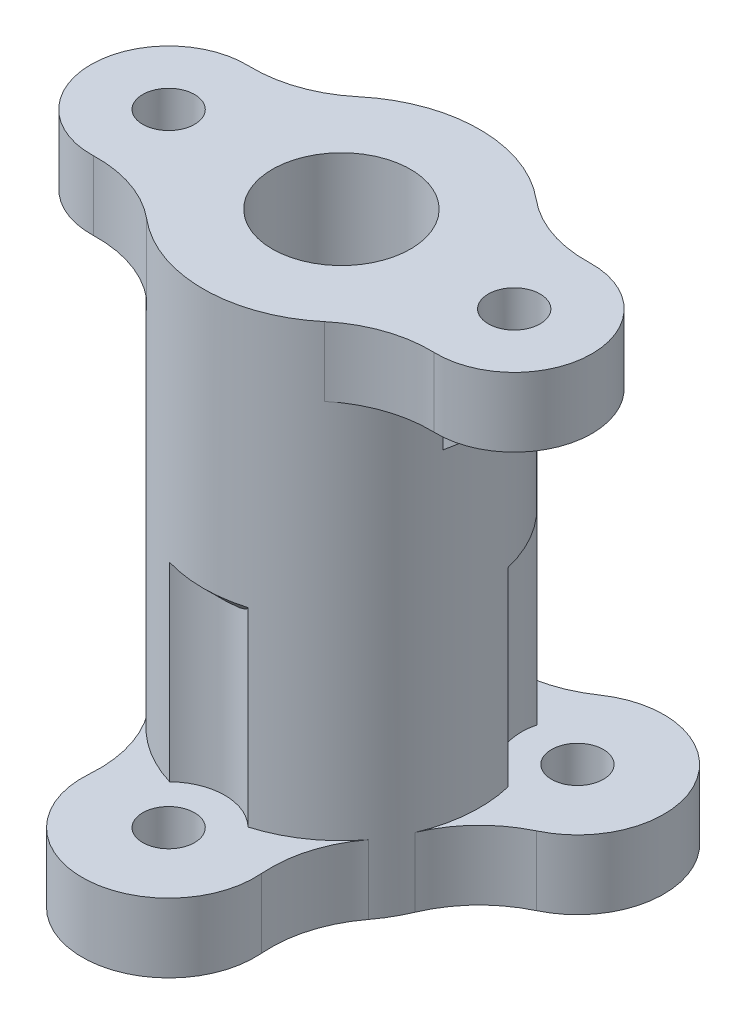
SolidWorks part; units mm, degrees
ref_plane "Спереди" through (0, 0, 0) normal (0, 0, 1) x (1, 0, 0)
ref_plane "Сверху" through (0, 0, 0) normal (0, 1, 0) x (1, 0, 0)
ref_plane "Справа" through (0, 0, 0) normal (1, 0, 0) x (0, 0, -1)
sketch "Sketch1" plane through (0, 0, 0) normal (0, 1, 0) x (1, 0, 0)
  circle A0 centre (0, 0) radius 4
  circle A1 centre (0, 0) radius 8
  dimension "D1" = 8
  dimension "D2" = 4
extrude "Boss-Extrude1" add sketch "Sketch1" along normal blind 30
sketch "Sketch2" plane through (0, 30, 0) normal (0, 1, 0) x (1, 0, 0)
  line L0 (0, 5.7735) -> (0, 0) construction
  circle A0 centre (-10, 0) radius 1.5
  circle A2 centre (-10, 0) radius 4.5
  circle A3 centre (10, 0) radius 4.5
  circle A4 centre (10, 0) radius 1.5
  dimension "D1" = 3
  dimension "D2" = 9
  dimension "D3" = 20
extrude "Boss-Extrude2" add sketch "Sketch2" against normal blind 4
fillet "Fillet1" radius 7 4 edges at (7.1875, 28, 3.5128) (7.1875, 28, -3.5128) (-7.1875, 28, -3.5128) (-7.1875, 28, 3.5128)
sketch "Sketch3" plane through (0, 0, 0) normal (0, -1, 0) x (1, 0, 0)
  circle A0 centre (0, 10) radius 1.5
  circle A1 centre (0, 10) radius 5
  circle A2 centre (8.6603, -5) radius 1.5
  circle A3 centre (8.6603, -5) radius 5
  circle A4 centre (-8.6603, -5) radius 1.5
  circle A5 centre (-8.6603, -5) radius 5
  point P13 (0, 0)
  dimension "D1" = 3
  dimension "D3" = 10
  dimension "D2" = 10
extrude "Boss-Extrude3" add sketch "Sketch3" against normal blind 4
fillet "Fillet2" radius 7 6 edges at (4.0379, 2, -6.9062) (-4.0379, 2, -6.9062) (-7.9999, 2, -0.0438) (-3.962, 2, 6.95) (7.9999, 2, -0.0438) (3.962, 2, 6.95)
sketch "Sketch4" plane through (0, 4, 0) normal (0, 1, 0) x (1, 0, 0)
  circle A0 centre (8.6603, 5) radius 3.25
  circle A1 centre (0, -10) radius 3.25
  circle A2 centre (-8.6603, 5) radius 3.25
  point P10 (0, 0)
  dimension "D1" = 6.5
extrude "Cut-Extrude1" cut sketch "Sketch4" along normal blind 10
chamfer "Chamfer1" distance 1 angle 45 3 edges at (-6.9282, 14, -4) (0, 14, 8) (6.9282, 14, -4)
sketch "Sketch5" plane through (0, 26, 0) normal (0, -1, 0) x (1, 0, 0)
  line L0 (0, 0) -> (0, 6.0381) construction
  line L1 (-10, 3.1754) -> (-12.75, 1.5877)
  line L2 (-12.75, 1.5877) -> (-12.75, -1.5877)
  line L3 (-12.75, -1.5877) -> (-10, -3.1754)
  line L4 (-10, -3.1754) -> (-7.25, -1.5877)
  line L5 (-7.25, -1.5877) -> (-7.25, 1.5877)
  line L6 (-7.25, 1.5877) -> (-10, 3.1754)
  line L7 (7.25, 1.5877) -> (10, 3.1754)
  line L8 (7.25, -1.5877) -> (7.25, 1.5877)
  line L9 (10, -3.1754) -> (7.25, -1.5877)
  line L10 (12.75, -1.5877) -> (10, -3.1754)
  line L11 (12.75, 1.5877) -> (12.75, -1.5877)
  line L12 (10, 3.1754) -> (12.75, 1.5877)
  circle A0 centre (-10, 0) radius 2.75 construction
  circle A1 centre (10, 0) radius 2.75 construction
  dimension "D1" = 5.5
extrude "Cut-Extrude2" cut sketch "Sketch5" against normal blind 1.5 and the other way blind 1.5
chamfer "Chamfer2" distance 1 angle 60 1 edges at (-8, 24.5, 0) first distance on face at (-7.5684, 24.5, 0)
chamfer "Chamfer3" distance 1 angle 60 1 edges at (8, 24.5, 0) first distance on face at (7.5684, 24.5, 0)
